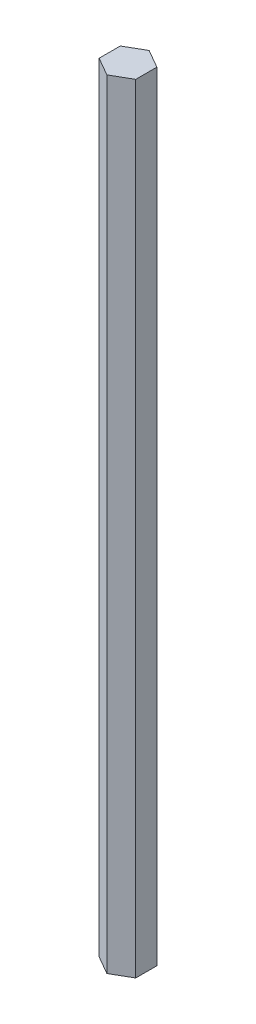
SolidWorks part; units mm, degrees
ref_plane "Front Plane" through (0, 0, 0) normal (0, 0, 1) x (1, 0, 0)
ref_plane "Top Plane" through (0, 0, 0) normal (0, 1, 0) x (1, 0, 0)
ref_plane "Right Plane" through (0, 0, 0) normal (1, 0, 0) x (0, 0, -1)
sketch "Sketch1" plane through (0, 0, 0) normal (0, 1, 0) x (1, 0, 0)
  line L1 (6.3495, -3.6671) -> (6.3505, 3.6653)
  line L2 (6.3505, 3.6653) -> (0.0011, 7.3323)
  line L3 (0.0011, 7.3323) -> (-6.3495, 3.6671)
  line L4 (-6.3495, 3.6671) -> (-6.3505, -3.6653)
  line L5 (-6.3505, -3.6653) -> (-0.0011, -7.3323)
  line L6 (-0.0011, -7.3323) -> (6.3495, -3.6671)
  circle A1 centre (0, 0) radius 6.35 construction
extrude "Boss-Extrude1" add sketch "Sketch1" along normal mid plane 270
ref_axis "Axis1" through (0, 176.9166, 0) along (0, -1, 0)
